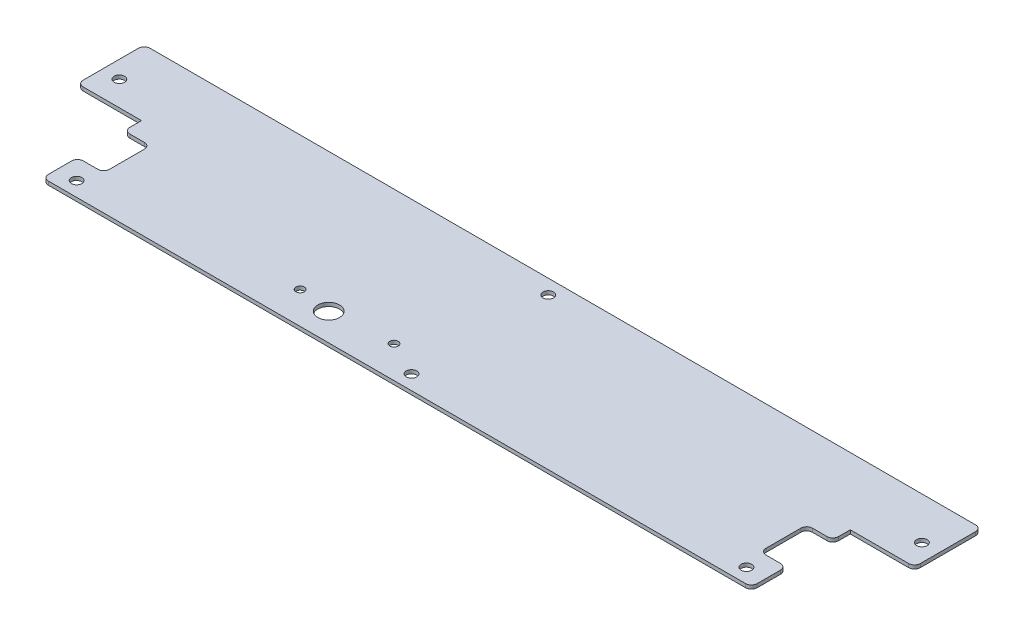
SolidWorks part; units mm, degrees
ref_plane "Front Plane" through (0, 0, 0) normal (0, 0, 1) x (1, 0, 0)
ref_plane "Top Plane" through (0, 0, 0) normal (0, 1, 0) x (1, 0, 0)
ref_plane "Right Plane" through (0, 0, 0) normal (1, 0, 0) x (0, 0, -1)
sketch "Sketch1" plane through (0, 0, 0) normal (0, 1, 0) x (1, 0, 0)
  line L0 (0, 0) -> (0, -29.845) construction
  line L1 (190.5, -36.195) -> (-190.5, -36.195) construction
  line L2 (190.5, -36.195) -> (190.5, 36.195) construction
  line L3 (190.5, 36.195) -> (-190.5, 36.195) construction
  line L4 (-190.5, -36.195) -> (-190.5, 36.195) construction
  line L5 (190.5, -36.195) -> (-190.5, 36.195) construction
  line L6 (190.5, 36.195) -> (-190.5, -36.195) construction
  line L7 (-146.177, -29.845) -> (146.177, -29.845) construction
  line L8 (0, 0) -> (0, 29.845) construction
  line L27 (0, 0) -> (0, 17.78) construction
  line L34 (-175.1457, 17.78) -> (175.1457, 17.78) construction
  line L35 (-154.686, -36.195) -> (-154.686, 6.985)
  line L48 (154.686, -36.195) -> (154.686, 6.985)
  line L49 (154.686, -36.195) -> (-154.686, -36.195)
  line L50 (-154.686, 6.985) -> (-182.7083, 6.985)
  line L52 (-182.7083, 36.195) -> (-182.7083, 6.985)
  line L53 (-182.7083, 36.195) -> (182.7083, 36.195)
  line L54 (182.7083, 36.195) -> (182.7083, 6.985)
  line L55 (182.7083, 6.985) -> (154.686, 6.985)
  circle A0 centre (175.1457, 17.78) radius 2.286
  circle A1 centre (0, 29.845) radius 2.286
  circle A2 centre (146.177, -29.845) radius 2.286
  circle A3 centre (-175.1457, 17.78) radius 2.286
  circle A4 centre (0, -29.845) radius 2.286
  circle A5 centre (-146.177, -29.845) radius 2.286
  point P0 (0, 0)
  point P10 (0, -29.845)
  point P21 (0, 36.195)
  point P22 (0, -36.195)
  point P58 (0, 17.78)
  dimension "D5" = 4.572
  dimension "D1" = 381
  dimension "D2" = 72.39
  dimension "D3" = 7.5626
  dimension "D4" = 8.509
  dimension "D6" = 29.845
  dimension "D7" = 17.78
  dimension "D8" = 35.814
  dimension "D10" = 6.35
  dimension "D11" = 43.18
  dimension "D12" = 43.18
  dimension "D13" = 28.0223
  dimension "D14" = 175.1457
  dimension "D15" = 175.1457
  dimension "D16" = 182.7083
  dimension "D17" = 182.7083
extrude "Boss-Extrude1" add sketch "Sketch1" along normal blind 1.5875
fillet "Fillet1" radius 2.54 6 edges at (182.7083, 0.7937, -6.985) (182.7083, 0.7937, -36.195) (154.686, 0.7937, 36.195) (-154.686, 0.7937, 36.195) (-182.7083, 0.7937, -36.195) (-182.7083, 0.7937, -6.985)
sketch "Sketch2" plane through (0, 1.5875, 0) normal (0, 1, 0) x (1, 0, 0)
  line L0 (-154.686, 6.985) -> (-154.686, -33.655) construction
  line L1 (-154.686, -0.635) -> (-143.256, -0.635)
  line L2 (-154.686, -0.635) -> (-154.686, -20.955)
  line L3 (-154.686, -20.955) -> (-143.256, -20.955)
  line L4 (-143.256, -0.635) -> (-143.256, -20.955)
  line L5 (154.686, -33.655) -> (154.686, 6.985) construction
  line L6 (154.686, -0.635) -> (143.256, -0.635)
  line L7 (154.686, -0.635) -> (154.686, -20.955)
  line L8 (154.686, -20.955) -> (143.256, -20.955)
  line L9 (143.256, -0.635) -> (143.256, -20.955)
  line L10 (-152.146, -36.195) -> (152.146, -36.195) construction
  dimension "D1" = 20.32
  dimension "D2" = 15.24
  dimension "D3" = 11.43
  dimension "D4" = 20.32
  dimension "D5" = 15.24
extrude "Cut-Extrude1" cut sketch "Sketch2" against normal blind 2.54
fillet "Fillet2" radius 2.54 8 edges at (154.686, 0.7937, 20.955) (143.256, 0.7937, 20.955) (143.256, 0.7937, 0.635) (154.686, 0.7937, 0.635) (-154.686, 0.7937, 20.955) (-143.256, 0.7937, 20.955) (-143.256, 0.7937, 0.635) (-154.686, 0.7937, 0.635)
sketch "Sketch3" plane through (0, 1.5875, 0) normal (0, 1, 0) x (1, 0, 0)
  line L0 (-56.2531, -22.225) -> (-15.2526, -22.225)
  line L2 (-41.7751, -24.2251) -> (-41.7751, -22.225)
  line L3 (-152.146, -36.195) -> (152.146, -36.195) construction
  circle A3 centre (-56.2531, -22.225) radius 1.83
  circle A4 centre (-15.2526, -22.225) radius 1.83
  circle A5 centre (-41.7751, -24.2251) radius 4.75
  point P8 (-90.4699, 23.0048)
  point P9 (-44.5098, -23.495)
  point P11 (-31.6647, -24.7331)
  point P12 (-22.9346, -24.7331)
  point P13 (-29.7528, -24.7331)
  dimension "D4" = 41.0005
  dimension "D5" = 2.0001
  dimension "D6" = 14.478
  dimension "D2" = 9.5001
  dimension "D3" = 3.66
  dimension "D1" = 13.97
extrude "Cut-Extrude2" cut sketch "Sketch3" against normal through all contours A4 | A3 | A5
